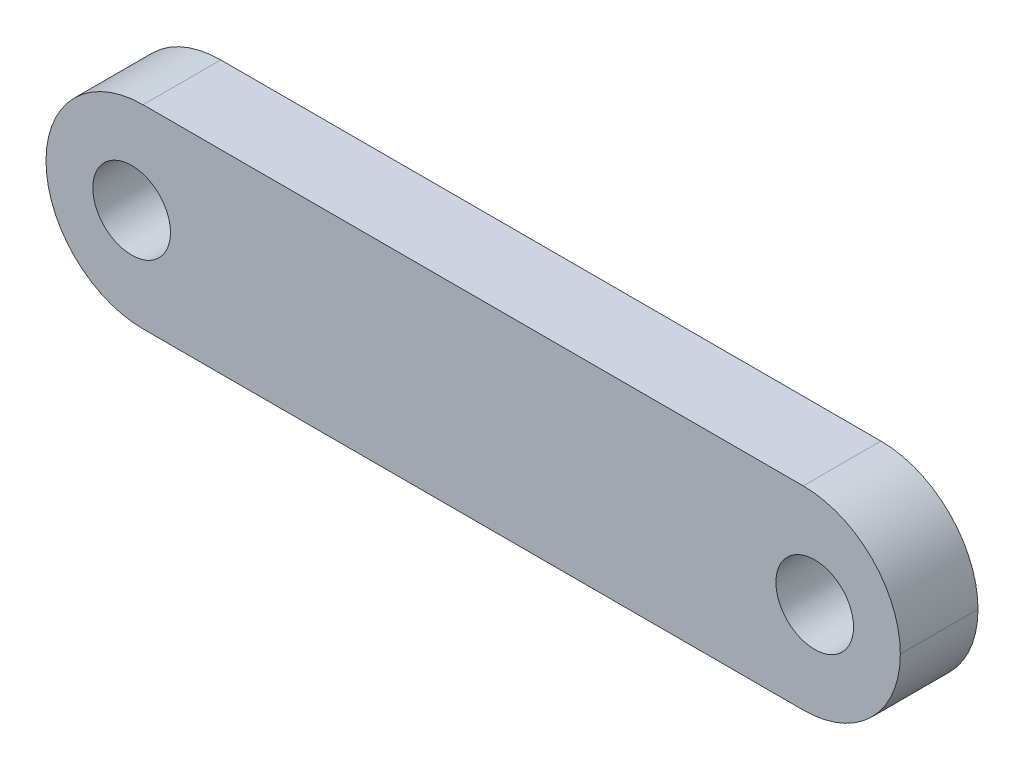
SolidWorks part; units mm, degrees
ref_plane "Front Plane" through (0, 0, 0) normal (0, 0, 1) x (1, 0, 0)
ref_plane "Top Plane" through (0, 0, 0) normal (0, 1, 0) x (1, 0, 0)
ref_plane "Right Plane" through (0, 0, 0) normal (1, 0, 0) x (0, 0, -1)
sketch "Sketch1" plane through (0, 0, 0) normal (0, 0, 1) x (1, 0, 0)
  line L0 (0, 6.5661) -> (0, -6.8711) construction
  line L1 (-11, 2.5) -> (11, 2.5)
  line L2 (-11, 2.5) -> (-11, -2.5)
  line L3 (-11, -2.5) -> (11, -2.5)
  line L4 (11, 2.5) -> (11, -2.5)
  line L5 (-11, 2.5) -> (11, -2.5) construction
  line L6 (-11, -2.5) -> (11, 2.5) construction
  circle A0 centre (8.795, 0) radius 1
  circle A1 centre (-8.795, 0) radius 1
  point P0 (0, 0)
  point P12 (-3.1102, 0)
  point P13 (8.795, 0)
  dimension "D1" = 22
  dimension "D2" = 5
extrude "Boss-Extrude1" add sketch "Sketch1" along normal blind 2
fillet "Fillet1" radius 2.5 4 edges at (-11, -2.5, 1) (-11, 2.5, 1) (11, -2.5, 1) (11, 2.5, 1)
